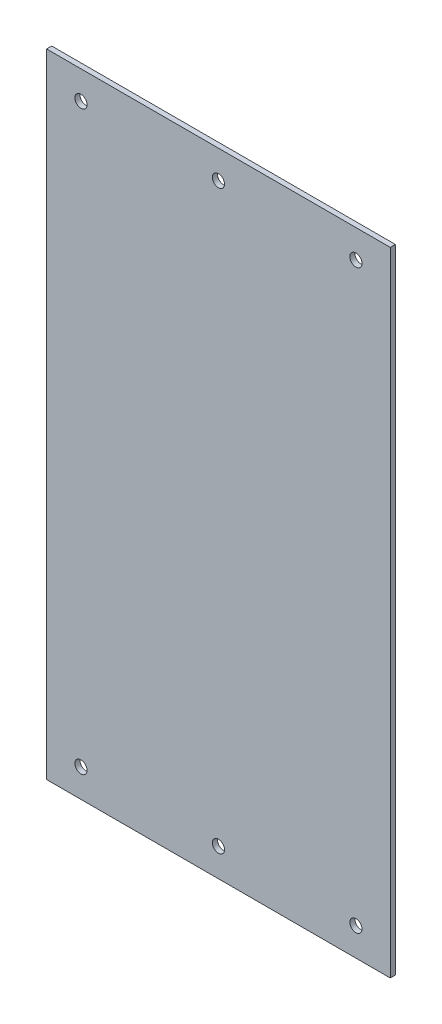
SolidWorks part; units mm, degrees
material "1060 Alloy"
ref_plane "Front Plane" through (0, 0, 0) normal (0, 0, 1) x (1, 0, 0)
ref_plane "Top Plane" through (0, 0, 0) normal (0, 1, 0) x (1, 0, 0)
ref_plane "Right Plane" through (0, 0, 0) normal (1, 0, 0) x (0, 0, -1)
sketch "Sketch1" plane through (0, 0, 0) normal (0, 0, 1) x (1, 0, 0)
  line L0 (55, 0) -> (-55, 0) construction
  line L1 (-77.5, 142.695) -> (77.5, 142.695)
  line L2 (-77.5, 142.695) -> (-77.5, -142.695)
  line L3 (-77.5, -142.695) -> (77.5, -142.695)
  line L4 (77.5, 142.695) -> (77.5, -142.695)
  line L5 (-77.5, 142.695) -> (77.5, -142.695) construction
  line L6 (-77.5, -142.695) -> (77.5, 142.695) construction
  point P0 (0, 0)
  point P5 (-62, 129.995)
  point P7 (0, 129.995)
  point P8 (62, 129.995)
  point P9 (0, 0)
  point P10 (0, 0)
  point P13 (62, -129.995)
  point P14 (0, -129.995)
  point P15 (-62, -129.995)
  dimension "D1" = 155
  dimension "D2" = 285.39
  dimension "D3" = 15.5
  dimension "D4" = 15.5
  dimension "D5" = 12.7
extrude "Boss-Extrude1" add sketch "Sketch1" along normal blind 2.305
hole_wizard "M5 Clearance Hole1" positions "Sketch2" profile "Sketch3" hole size "M5" standard "ANSI Metric" end condition through all
sketch "Sketch2" plane through (0, 0, 2.305) normal (0, 0, 1) x (1, 0, 0)
  point P0 (-62, 129.995)
  point P3 (0, 129.995)
  point P6 (62, 129.995)
  point P9 (-62, -129.995)
  point P12 (0, -129.995)
  point P15 (62, -129.995)
sketch "Sketch3" plane through (-62, 129.995, 2.305) normal (1, 0, 0) x (0, -1, 0)
  line L0 (0, 0) -> (0, 2.305)
  line L1 (0, 2.305) -> (2.75, 2.305)
  line L2 (2.75, 2.305) -> (2.75, 0)
  line L5 (2.75, 0) -> (0, 0)
  line L11 (0, -6.35) -> (0, 107.95) construction
  dimension "Thru Hole Dia." = 5.5
  dimension "Thru Hole Depth" = 2.305
